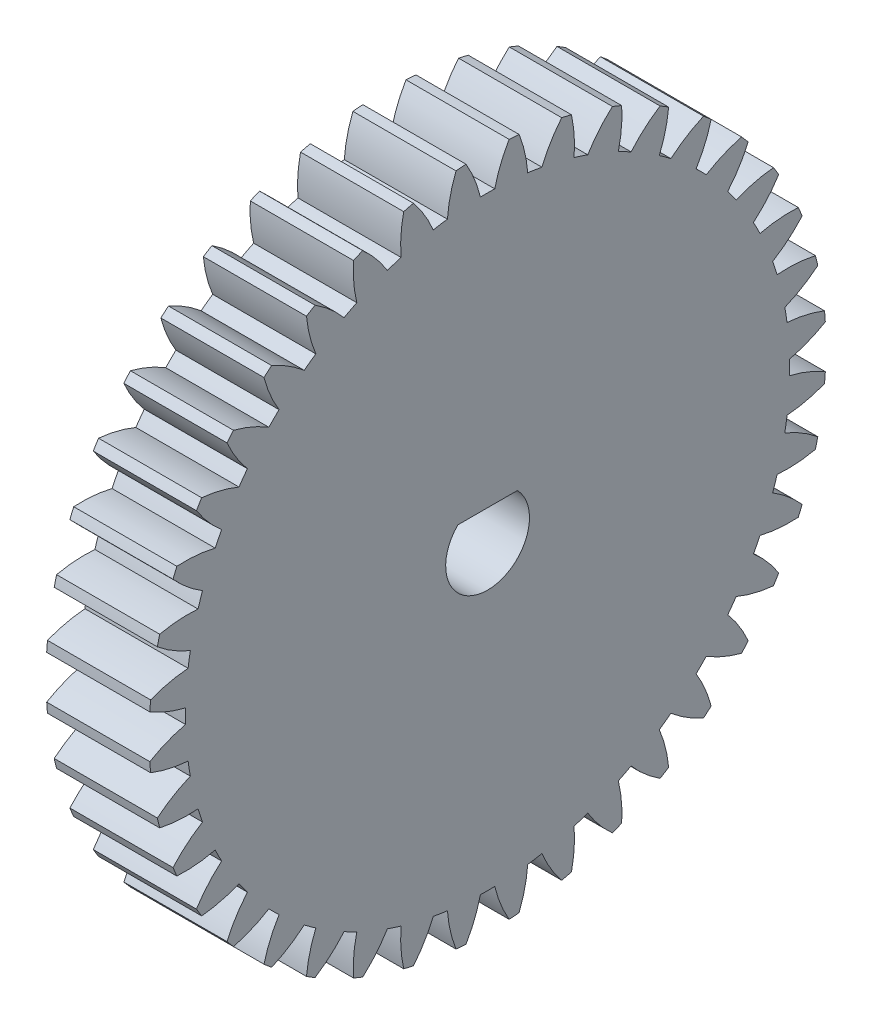
SolidWorks part; units mm, degrees
ref_plane "Plane1" through (0, 0, 0) normal (0, 0, 1) x (1, 0, 0)
ref_plane "Plane2" through (0, 0, 0) normal (0, 1, 0) x (1, 0, 0)
ref_plane "Plane3" through (0, 0, 0) normal (1, 0, 0) x (0, 0, -1)
sketch "HoldingSke" plane through (0, 0, 0) normal (0, 1, 0) x (1, 0, 0)
  line L0 (0, 0) -> (0.6128, -0.5142)
  line L1 (-15, 0) -> (100, 0) construction
  line L2 (0, 0) -> (-2.1039, 2.3779)
  line L3 (0, 0) -> (-11.863, 4.5341)
  line L4 (0, 0) -> (6.6156, 5.5511)
  line L5 (0, 0) -> (-46.8476, -17.4728)
  line L6 (0, 0) -> (-6.6317, -4.4744)
  line L7 (-2.1039, 2.3779) -> (8.6586, 51.2059)
  line L8 (-76.2, 54.61) -> (-75.2, 54.61)
  line L9 (-71.009, 38.7566) -> (-53.1078, 45.2721)
  line L10 (-76.2, 71.12) -> (104.1128, 71.12)
  line L11 (0, 0) -> (-8, 0)
  line L12 (-76.2, 101.6) -> (-76.155, 101.6)
  line L13 (24.9733, 27.94) -> (52.9518, 28.4284)
  line L14 (24.9733, 27.94) -> (24.9743, 27.94)
  line L15 (24.9733, 27.94) -> (100.4006, 29.5858)
  line L16 (-63.627, -1.25) -> (-12.827, -1.25)
  circle A0 centre (0, 0) radius 3.5
  circle A1 centre (0, 0) radius 23.4365
  circle A2 centre (0, 0) radius 37.5
  circle A3 centre (0, 0) radius 3.5
  dimension "Num_teeth" = 40
  dimension "Pitch_radius" = 180.3128
  dimension "Width" = 8
  dimension "Thickness" = 8
sketch "BasProSke" plane through (0, 0, 0) normal (0, 1, 0) x (1, 0, 0)
  line L0 (-10, 0) -> (60, 0) construction
  line L1 (0, 0) -> (0, 26.25)
  line L2 (0, 0) -> (8, 0)
  line L3 (8, 0) -> (8, 26.25)
  line L4 (8, 26.25) -> (0, 26.25)
  dimension "Thickness" = 8
  dimension "Diameter" = 52.5
revolve "Base-Revolve" add sketch "BasProSke" angle 360 about L0
sketch "TooCutSke" plane through (0, 0, 0) normal (1, 0, 0) x (0, 0, -1)
  line L1 (0, 0) -> (0, 107) construction
  line L2 (0, 0) -> (-1.0602, 24.9775) construction
  line L3 (0, 0) -> (-3.9204, 49.8134) construction
  line L4 (-1.0602, 24.9775) -> (-1.9602, 24.9067) construction
  arc A0 (0.5568, 23.4299) -> (-0.5568, 23.4299) centre (0, 0) ccw
  arc A1 (1.6852, 26.2213) -> (-1.6852, 26.2213) centre (0, 0) ccw
  circle A2 centre (0, 0) radius 25 construction
  circle A3 centre (0, 0) radius 23.4923 construction
  arc A4 (-0.5568, 23.4299) -> (-1.6852, 26.2213) centre (-10.2865, 21.1205) ccw
  arc A5 (1.6852, 26.2213) -> (0.5568, 23.4299) centre (10.2865, 21.1205) ccw
extrude "ToothCut" cut sketch "TooCutSke" along normal through all
fillet "Breaks" [suppressed] radius 0.025 tangent propagation no
fillet "RootFillets" [suppressed] radius 0.3135
pattern_circular "TeethCuts" count 40 every 9 about axis through (-10, 0, 0) along (1, 0, 0) of "ToothCut", "RootFillets", "Breaks"
sketch "HubNeaOneSke" plane through (0, 0, 0) normal (-1, 0, 0) x (0, 0, 1)
  circle A0 centre (0, 0) radius 23.4365
  dimension "Diameter" = 46.873
extrude "HubNearOne" [suppressed] add sketch "HubNeaOneSke" along normal blind 42.0001
sketch "HubNeaBotSke" plane through (0, 0, 0) normal (-1, 0, 0) x (0, 0, 1)
  circle A0 centre (0, 0) radius 23.4365
  dimension "Diameter" = 46.873
extrude "HubNearBoth" [suppressed] add sketch "HubNeaBotSke" along normal blind 21
ref_plane "FarPln" through (8, 0, 0) normal (1, 0, 0) x (0, 0, -1)
sketch "HubFarSke" plane through (8, 0, 0) normal (1, 0, 0) x (0, 0, -1)
  circle A0 centre (0, 0) radius 23.4365
  dimension "Diameter" = 46.873
extrude "HubFar" [suppressed] add sketch "HubFarSke" along normal blind 21
sketch "BorSke" plane through (0, 0, 0) normal (1, 0, 0) x (0, 0, -1)
  circle A0 centre (0, 0) radius 3.5
  dimension "Diameter" = 7
extrude "Bore" cut sketch "BorSke" along normal mid plane 100.0001
sketch "KeySke" plane through (0, 0, 0) normal (1, 0, 0) x (0, 0, -1)
  line L0 (-1, 0) -> (-1, 4.5)
  line L1 (-1, 4.5) -> (1, 4.5)
  line L2 (1, 4.5) -> (1, 0)
  line L3 (0, 0) -> (0, 34) construction
  line L4 (-1, 0) -> (1, 0)
  dimension "Width" = 2
extrude "Keyway" [suppressed] cut sketch "KeySke" along normal mid plane 100.0001
pattern_circular "Keyway2" [suppressed] count 2 every 90 about axis through (-10, 0, 0) along (1, 0, 0) reverse direction yes
sketch "Sketch1" plane through (8, 0, 0) normal (1, 0, 0) x (0, 0, -1)
  line L0 (-2.65, 2.2864) -> (2.65, 2.2864)
  circle A0 centre (0, 0) radius 3.5 construction
  circle A1 centre (0, 0) radius 3.5
  circle A2 centre (0, 0) radius 3.25
  point P5 (0, -3.5)
  dimension "D2" = 6.5
  dimension "D1" = 5.3
extrude "Boss-Extrude1" add sketch "Sketch1" against normal up to surface (8 mm away) contours L0 A2 | A2 L0 A1 | A2 L0 A1 region at (8, 3.4456, 0) region at (8, 2.1956, 2.4799) region at (8, 2.6772, 0) up to face at (0, 0, -3.5)
equation "' \"Module@HoldingSke\" = 6.35"
equation "' \"Num_teeth@HoldingSke\" = 12"
equation "' \"Ap@HoldingSke\" =  20"
equation "' \"Ap@HoldingSke\" = 20"
equation "' \"Width@HoldingSke\" = 0.5 * 25.4"
equation "' \"Hub_dia@HoldingSke\"= 1 * 25.4"
equation "' \"Hub_dia@HoldingSke\" = 1 * 25.4"
equation "' \"Overall_len@HoldingSke\" = 1.0 * 25.4"
equation "' \"Bore@HoldingSke\" = 0.75 * 25.4"
equation "' \"T_dim@HoldingSke\" = 0.1 * 25.4"
equation "' \"Width@KeySke\" = 0.25 * 25.4"
equation "' \"Show_teeth@HoldingSke\" = 13"
equation "' \"Backlash@HoldingSke\" = 0.009 * 25.4"
equation "' \"Addendum_fac@HoldingSke\" = 1.0"
equation "' \"Dedendum_fac@HoldingSke\" = 1.25"
equation "' \"Dedendum_add@HoldingSke\" = 0.00005 * 25.4"
equation "' \"Clearance_fac@HoldingSke\" = 0.25"
equation "\"Pitch@HoldingSke\" = 1 / \"Module@HoldingSke\""
equation "\"Overcut_dia@TooCutSke\" = (\"Num_teeth@HoldingSke\" + 2 * \"Addendum_fac@HoldingSke\") / \"Pitch@HoldingSke\" + 0.002 * 25.4"
equation "\"Pitch_dia@TooCutSke\" = \"Num_teeth@HoldingSke\" / \"Pitch@HoldingSke\""
equation "\"Base_dia@TooCutSke\" = \"Num_teeth@HoldingSke\" / \"Pitch@HoldingSke\" * cos((\"Ap@HoldingSke\"  * 3.14159265 / 180))"
equation "\"Root_dia@TooCutSke\" = (\"Num_teeth@HoldingSke\" + 2) / \"Pitch@HoldingSke\" - 2 * (\"Addendum_fac@HoldingSke\" + \"Dedendum_fac@HoldingSke\") / \"Pitch@HoldingSke\" - \"Dedendum_add@HoldingSke\" * 2"
equation "\"Half_ang@TooCutSke\" = 180 / \"Num_teeth@HoldingSke\""
equation "\"Half_CT@TooCutSke\" = \"Num_teeth@HoldingSke\" / \"Pitch@HoldingSke\" * sin((3.14159265 / 2 / \"Num_teeth@HoldingSke\")) / 2 - 7 * \"Backlash@HoldingSke\" / 4"
equation "\"Flank_rad@TooCutSke\" = \"Num_teeth@HoldingSke\" / \"Pitch@HoldingSke\" / 5"
equation "\"Radius@RootFillets\" = \"Clearance_fac@HoldingSke\" / \"Pitch@HoldingSke\" + \"Dedendum_add@HoldingSke\""
equation "\"Break_rad@Breaks\" = 0.02 / \"Pitch@HoldingSke\""
equation "\"Thickness@HoldingSke\" = \"Width@HoldingSke\""
equation "\"OAL@HoldingSke\" = \"Thickness@HoldingSke\""
equation "\"MHD@HoldingSke\" = (\"Num_teeth@HoldingSke\" + 2) / \"Pitch@HoldingSke\" - 2 * (\"Addendum_fac@HoldingSke\" + \"Dedendum_fac@HoldingSke\")  / \"Pitch@HoldingSke\" - \"Dedendum_add@HoldingSke\" * 2"
equation "\"MBD@HoldingSke\" = (\"Num_teeth@HoldingSke\" + 2) / \"Pitch@HoldingSke\" - 2 * (\"Addendum_fac@HoldingSke\" + \"Dedendum_fac@HoldingSke\")  / \"Pitch@HoldingSke\" - \"Dedendum_add@HoldingSke\" * 2 - 0.002 * 25.4"
equation "\"MHD@HoldingSke\" = ((sgn( \"MHD@HoldingSke\" - \"Hub_dia@HoldingSke\" )-1)*( \"MHD@HoldingSke\" - \"Hub_dia@HoldingSke\" ))/-2+ \"Hub_dia@HoldingSke\""
equation "\"MBD@HoldingSke\" = ((sgn( \"MBD@HoldingSke\" - \"Bore@HoldingSke\" )-1)*( \"MBD@HoldingSke\" - \"Bore@HoldingSke\" ))/-2+ \"Bore@HoldingSke\""
equation "\"OAL@HoldingSke\" = ((sgn( \"OAL@HoldingSke\" - \"Overall_len@HoldingSke\" )+1)*( \"OAL@HoldingSke\" - \"Overall_len@HoldingSke\" ))/2 + \"Overall_len@HoldingSke\" + 0.000002 * 25.4"
equation "\"Num_teeth@TeethCuts\" = int( \"Show_teeth@HoldingSke\" ) + 1"
equation "\"Num_teeth@TeethCuts\" = ((sgn( \"Num_teeth@TeethCuts\" - \"Num_teeth@HoldingSke\" )-1)*( \"Num_teeth@TeethCuts\" - \"Num_teeth@HoldingSke\" ))/-2+ \"Num_teeth@HoldingSke\""
equation "\"Num_teeth@TeethCuts\" = ((sgn( \"Num_teeth@TeethCuts\" - 2.0)+1)*( \"Num_teeth@TeethCuts\" - 2.0))/2 +2.0"
equation "\"Angle@TeethCuts\" = 360.0 / \"Num_teeth@HoldingSke\""
equation "\"Diameter@BasProSke\" = (\"Num_teeth@HoldingSke\" + 2 * \"Addendum_fac@HoldingSke\") / \"Pitch@HoldingSke\""
equation "\"Thickness@BasProSke\"  = \"Thickness@HoldingSke\""
equation "' \"Fillet_rad@BasProSke\" =  \"Thickness@HoldingSke\" * 0.05"
equation "' \"Fillet_rad@BasProSke\" = \"Thickness@HoldingSke\" * 0.05"
equation "\"MHD@HoldingSke\" = ((sgn( \"MHD@HoldingSke\" - \"Root_dia@TooCutSke\" )-1)*( \"MHD@HoldingSke\" - \"Root_dia@TooCutSke\" ))/-2+ \"Root_dia@TooCutSke\""
equation "\"Diameter@HubNeaOneSke\" = \"MHD@HoldingSke\""
equation "\"Length@HubNearOne\" = \"OAL@HoldingSke\" - \"Thickness@BasProSke\""
equation "\"Diameter@HubNeaBotSke\" = \"MHD@HoldingSke\""
equation "\"Length@HubNearBoth\" = ( \"OAL@HoldingSke\" - \"Thickness@BasProSke\" ) / 2.0"
equation "\"Thickness@FarPln\" = \"Thickness@BasProSke\""
equation "\"Diameter@HubFarSke\" = \"MHD@HoldingSke\""
equation "\"Length@HubFar\" = ( \"OAL@HoldingSke\" - \"Thickness@BasProSke\" ) / 2.0"
equation "\"Diameter@BorSke\" = \"MBD@HoldingSke\""
equation "\"D1@Bore\" = \"OAL@HoldingSke\" * 2.0"
equation "\"D1@Keyway\" = \"OAL@HoldingSke\" * 2.0"
equation "\"Offset@KeySke\" = \"T_dim@HoldingSke\" + \"MBD@HoldingSke\" / 2.0"
